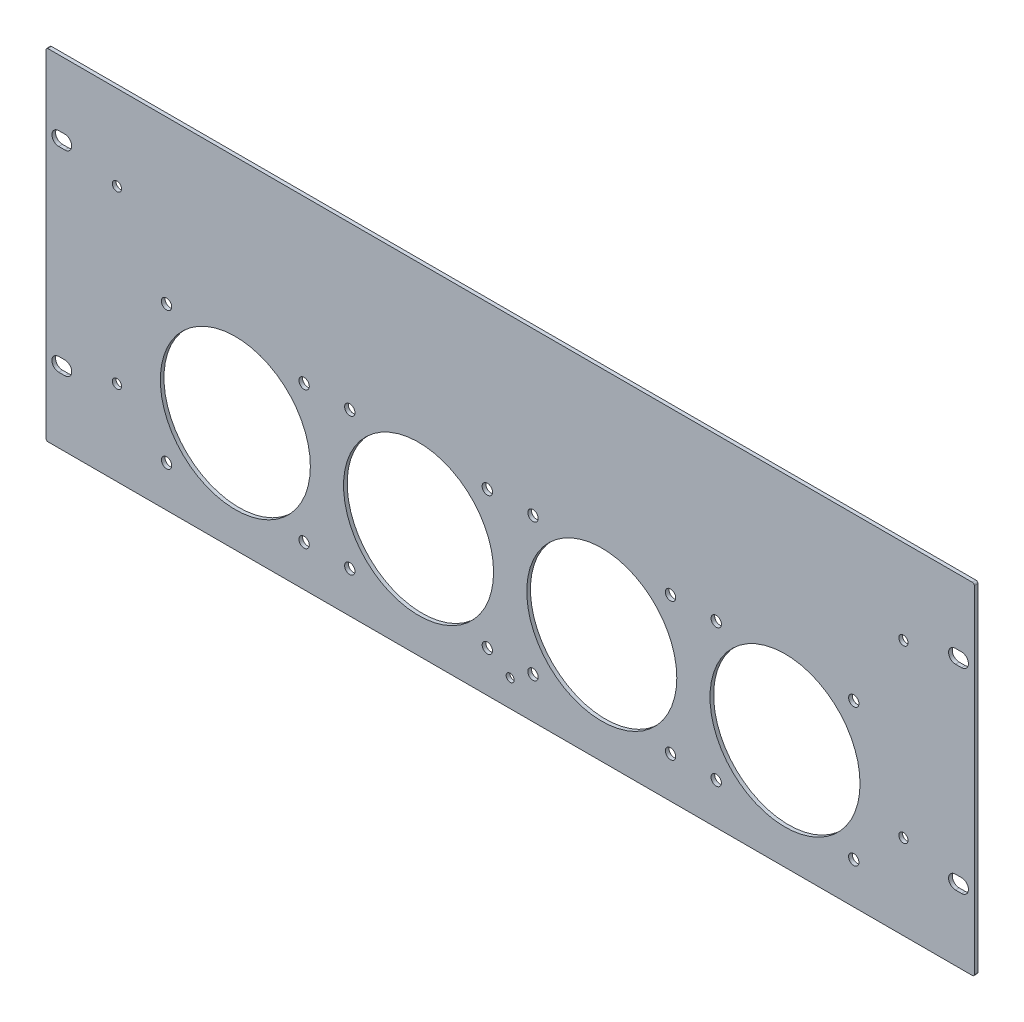
SolidWorks part; units mm, degrees
ref_plane "Front" through (0, 0, 0) normal (0, 0, 1) x (1, 0, 0)
ref_plane "Top" through (0, 0, 0) normal (0, 1, 0) x (1, 0, 0)
ref_plane "Right" through (0, 0, 0) normal (1, 0, 0) x (0, 0, -1)
sketch "Sketch1" plane through (0, 0, 0) normal (0, 0, 1) x (1, 0, 0)
  line L0 (0, 0) -> (0, 3.175) construction
  line L1 (-240.284, 0) -> (240.284, 0)
  line L2 (-241.3, 1.016) -> (-241.3, 176.022)
  line L3 (-240.284, 177.038) -> (240.284, 177.038)
  line L4 (241.3, 1.016) -> (241.3, 176.022)
  arc A0 (-241.3, 176.022) -> (-240.284, 177.038) centre (-240.284, 176.022) cw
  arc A1 (-240.284, 0) -> (-241.3, 1.016) centre (-240.284, 1.016) cw
  arc A2 (240.284, 0) -> (241.3, 1.016) centre (240.284, 1.016) ccw
  arc A3 (240.284, 177.038) -> (241.3, 176.022) centre (240.284, 176.022) cw
  point P6 (-241.3, 177.038)
  point P9 (-241.3, 0)
  point P12 (241.3, 0)
  dimension "D3" = 1.016
  dimension "D1" = 3.175
  dimension "U Height" = 177.038
  dimension "Panel Std Width" = 482.6
sheet metal parameters "Sheet-Metal1" thickness 1.905 parameters "D1"=1.651
base flange "Front Panel" sketch "Sketch1" thickness 1.905 parameters "D1"=1.651
sketch "Sketch2" plane through (0, 0, 1.905) normal (0, 0, 1) x (1, 0, 0)
  line L0 (-233.0704, 142.9004) -> (-233.0704, 135.7884) construction
  line L1 (-241.3, 176.022) -> (-241.3, 1.016) construction
  line L2 (241.3, 88.519) -> (-241.3, 88.519) construction
  line L3 (231.4702, 135.7884) -> (234.6706, 135.7884)
  line L4 (0, 177.038) -> (0, 0) construction
  line L5 (240.284, 177.038) -> (-240.284, 177.038) construction
  line L6 (234.6706, 142.9004) -> (231.4702, 142.9004)
  line L7 (-231.4702, 41.2496) -> (-234.6706, 41.2496)
  line L8 (-234.6706, 34.1376) -> (-231.4702, 34.1376)
  line L9 (-234.6706, 142.9004) -> (-231.4702, 142.9004)
  line L10 (-231.4702, 135.7884) -> (-234.6706, 135.7884)
  line L11 (-240.284, 0) -> (240.284, 0) construction
  line L12 (234.6706, 34.1376) -> (231.4702, 34.1376)
  line L13 (231.4702, 41.2496) -> (234.6706, 41.2496)
  line L22 (241.3, 1.016) -> (241.3, 176.022) construction
  arc A0 (231.4702, 135.7884) -> (231.4702, 142.9004) centre (231.4702, 139.3444) cw
  arc A1 (234.6706, 142.9004) -> (234.6706, 135.7884) centre (234.6706, 139.3444) cw
  arc A2 (-231.4702, 41.2496) -> (-231.4702, 34.1376) centre (-231.4702, 37.6936) cw
  arc A3 (-234.6706, 34.1376) -> (-234.6706, 41.2496) centre (-234.6706, 37.6936) cw
  arc A4 (-234.6706, 142.9004) -> (-234.6706, 135.7884) centre (-234.6706, 139.3444) ccw
  arc A5 (-231.4702, 135.7884) -> (-231.4702, 142.9004) centre (-231.4702, 139.3444) ccw
  arc A6 (234.6706, 34.1376) -> (234.6706, 41.2496) centre (234.6706, 37.6936) ccw
  arc A7 (231.4702, 41.2496) -> (231.4702, 34.1376) centre (231.4702, 37.6936) ccw
  point P32 (-227.9142, 139.3444)
  point P39 (-238.2266, 139.3444)
  dimension "D1" = 3.2004
  dimension "D2" = 37.6936
  dimension "D3" = 13.3858
  dimension "Slot Radius" = 3.556
extrude "Rack Mounting Slot" cut sketch "Sketch2" against normal blind 1.905 normal cut yes
sketch "Sketch3" plane through (0, 0, 1.905) normal (0, 0, 1) x (1, 0, 0)
  circle A0 centre (-204.4192, 132.969) radius 2.3876
  circle A1 centre (-204.4192, 44.069) radius 2.3876
  circle A2 centre (0, 13.9192) radius 2.0701
  circle A3 centre (204.4192, 44.069) radius 2.3876
  circle A4 centre (204.4192, 132.969) radius 2.3876
  dimension "D1" = 4.1402
  dimension "D2" = 4.7752
extrude "Cut-Extrude1" cut sketch "Sketch3" against normal blind 1.905 normal cut yes
sketch "Sketch4" plane through (0, 0, 1.905) normal (0, 0, 1) x (1, 0, 0)
  line L2 (0, 177.038) -> (0, 0) construction
  line L3 (240.284, 177.038) -> (-240.284, 177.038) construction
  line L4 (-240.284, 0) -> (240.284, 0) construction
  circle B0 centre (-107.125, 92.9) radius 2.6924
  circle B1 centre (-178.625, 92.9) radius 2.6924
  circle B2 centre (-107.125, 21.4) radius 2.6924
  circle B3 centre (-178.625, 21.4) radius 2.6924
  circle B4 centre (-142.875, 57.15) radius 39.0017
  circle B5 centre (-11.875, 92.9) radius 2.6924
  circle B6 centre (-83.375, 92.9) radius 2.6924
  circle B7 centre (-11.875, 21.4) radius 2.6924
  circle B8 centre (-83.375, 21.4) radius 2.6924
  circle B9 centre (-47.625, 57.15) radius 39.0017
  circle B10 centre (83.375, 92.9) radius 2.6924
  circle B11 centre (11.875, 92.9) radius 2.6924
  circle B12 centre (83.375, 21.4) radius 2.6924
  circle B13 centre (11.875, 21.4) radius 2.6924
  circle B14 centre (47.625, 57.15) radius 39.0017
  circle B15 centre (178.625, 92.9) radius 2.6924
  circle B16 centre (107.125, 92.9) radius 2.6924
  circle B17 centre (178.625, 21.4) radius 2.6924
  circle B18 centre (107.125, 21.4) radius 2.6924
  circle B19 centre (142.875, 57.15) radius 39.0017
  dimension "D1" = 95.25
  dimension "D2" = 95.25
  dimension "D3" = 57.15
sketch_block_instance "80mm-openfan-1"
sketch_block "80mm-openfan" parameters "D1"=5.3848, "D4"=78.0034, "D2"=71.5, "D3"=71.5
sketch_block_instance "80mm-openfan-2"
sketch_block_instance "80mm-openfan-3"
sketch_block_instance "80mm-openfan-4"
extrude "Cut-Extrude4" cut sketch "Sketch4" against normal blind 1.905 normal cut yes
flat pattern "Flat-Pattern1" [suppressed]
sketch "Bend-Lines1" plane through (0, 0, 0) normal (0, 1, 0) x (-1, 0, 0)
